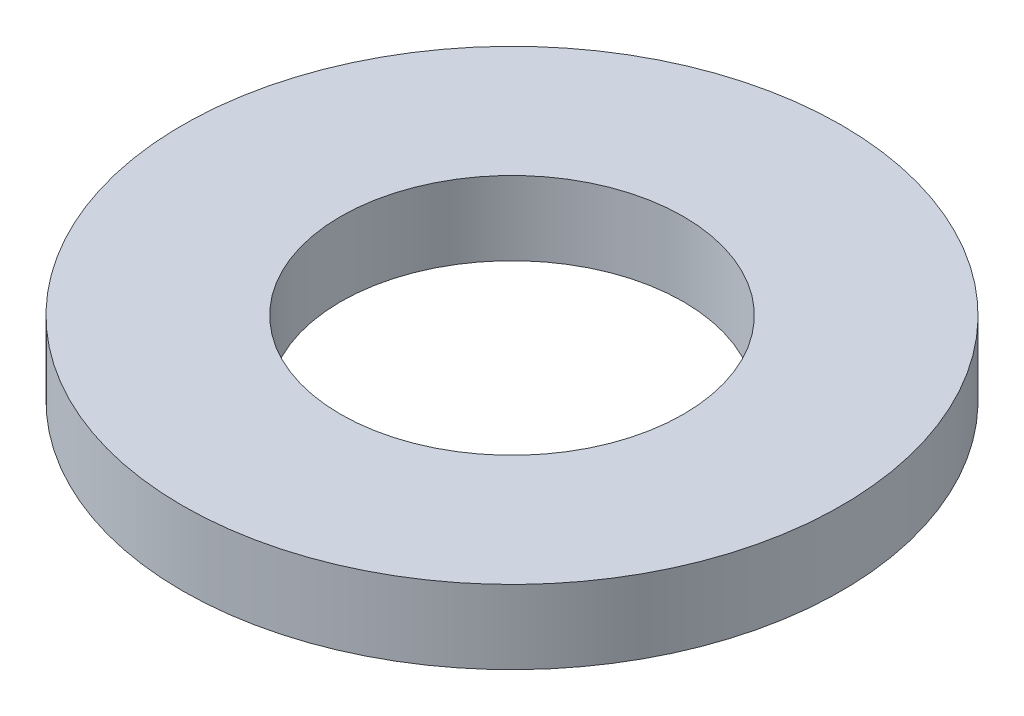
SolidWorks part; units mm, degrees
ref_plane "Front Plane" through (0, 0, 0) normal (0, 0, 1) x (1, 0, 0)
ref_plane "Top Plane" through (0, 0, 0) normal (0, 1, 0) x (1, 0, 0)
ref_plane "Right Plane" through (0, 0, 0) normal (1, 0, 0) x (0, 0, -1)
sketch "Sketch1" plane through (0, 0, 0) normal (0, 1, 0) x (1, 0, 0)
  circle A0 centre (0, 0) radius 62.5
  dimension "FLANGE_OD" = 125
extrude "Boss-Extrude1" add sketch "Sketch1" along normal blind 14
sketch "Sketch2" plane through (0, 0, 0) normal (0, 1, 0) x (1, 0, 0)
  circle A0 centre (0, 0) radius 32.5
  dimension "BORE_D" = 65
extrude "Cut-Extrude1" cut sketch "Sketch2" along normal through all
sketch "Sketch3" plane through (0, 14, 0) normal (0, 1, 0) x (1, 0, 0)
  circle A0 centre (0, 0) radius 26.5086 construction
  circle A1 centre (-26.5086, 0) radius 2.5122
  dimension "BOLT_D" = 5.0244
  dimension "BOLT_PCD" = 53.0172
extrude "Cut-Extrude2" cut sketch "Sketch3" against normal blind 13.8701 rebuild error yes
pattern_circular "CirPattern1" count 3 over 360 rebuild error yes
